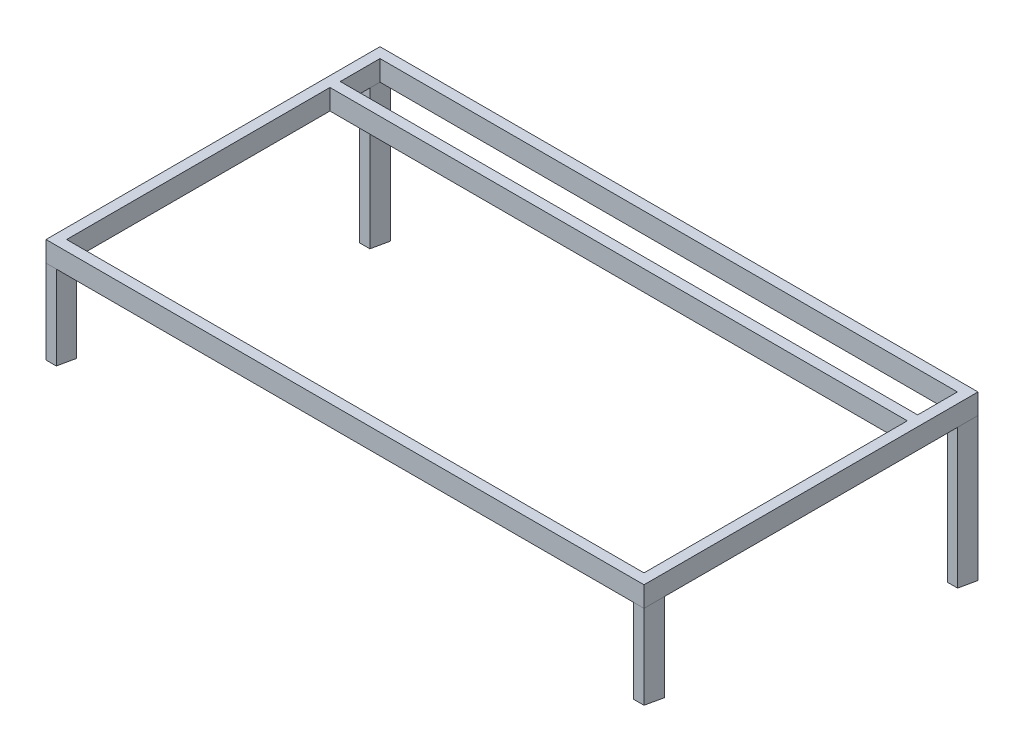
SolidWorks part; units mm, degrees
ref_plane "Front Plane" through (0, 0, 0) normal (0, 0, 1) x (1, 0, 0)
ref_plane "Top Plane" through (0, 0, 0) normal (0, 1, 0) x (1, 0, 0)
ref_plane "Right Plane" through (0, 0, 0) normal (1, 0, 0) x (0, 0, -1)
sketch "Sketch22" plane through (0, 0, 0) normal (0, 1, 0) x (1, 0, 0)
  line L0 (-712.1, 386.52) -> (712.1, 386.52)
  line L1 (-737.5, 411.92) -> (737.5, 411.92)
  line L2 (-737.5, 411.92) -> (-737.5, -411.92)
  line L3 (-737.5, -411.92) -> (737.5, -411.92)
  line L4 (737.5, 411.92) -> (737.5, -411.92)
  line L5 (-737.5, 411.92) -> (737.5, -411.92) construction
  line L6 (-737.5, -411.92) -> (737.5, 411.92) construction
  line L7 (712.1, 386.52) -> (712.1, -386.52)
  line L8 (-712.1, -386.52) -> (712.1, -386.52)
  line L9 (-712.1, 386.52) -> (-712.1, -386.52)
  point P0 (0, 0)
  dimension "D1" = 1475
  dimension "D2" = 823.84
  dimension "D3" = 25.4
extrude "Boss-Extrude3" add sketch "Sketch22" against normal blind 50.4
sketch "Sketch23" plane through (0, -50.4, 0) normal (0, -1, 0) x (1, 0, 0)
  line L0 (-712.1, -386.52) -> (-712.1, 386.52) construction
  line L1 (-737.5, 411.92) -> (-712.1, 411.92)
  line L2 (-737.5, 411.92) -> (-737.5, 361.52)
  line L3 (-737.5, 361.52) -> (-712.1, 361.52)
  line L4 (-712.1, 411.92) -> (-712.1, 361.52)
  line L5 (0, 0) -> (0, 277.5925) construction
  line L6 (712.1, 411.92) -> (712.1, 361.52)
  line L7 (737.5, 361.52) -> (712.1, 361.52)
  line L8 (737.5, 411.92) -> (737.5, 361.52)
  line L9 (737.5, 411.92) -> (712.1, 411.92)
  dimension "D1" = 50.4
extrude "Boss-Extrude4" add sketch "Sketch23" along normal blind 258.12 separate body
sketch "Sketch24" plane through (0, -50.4, 0) normal (0, -1, 0) x (1, 0, 0)
  line L0 (-712.1, -386.52) -> (-712.1, 386.52) construction
  line L1 (-737.5, -411.92) -> (-712.1, -411.92)
  line L2 (-737.5, -411.92) -> (-737.5, -361.52)
  line L3 (-737.5, -361.52) -> (-712.1, -361.52)
  line L4 (-712.1, -411.92) -> (-712.1, -361.52)
  line L5 (0, 0) -> (0, -131.3731) construction
  line L6 (712.1, -411.92) -> (712.1, -361.52)
  line L7 (737.5, -361.52) -> (712.1, -361.52)
  line L8 (737.5, -411.92) -> (737.5, -361.52)
  line L9 (737.5, -411.92) -> (712.1, -411.92)
  dimension "D1" = 50.4
extrude "Boss-Extrude5" add sketch "Sketch24" along normal blind 402.27 separate body
sketch "Sketch25" plane through (737.5, 0, 0) normal (1, 0, 0) x (0, 0, -1)
  line L0 (361.52, -393.9384) -> (411.92, -402.8253)
  line L2 (361.52, -452.67) -> (361.52, -50.4) construction
  line L3 (411.92, -452.67) -> (411.92, -50.4) construction
  line L4 (411.92, -402.8253) -> (411.92, -452.67)
  line L5 (411.92, -452.67) -> (-411.92, -452.67)
  line L6 (-411.92, -452.67) -> (-411.92, -257.5601)
  line L7 (-411.92, -308.52) -> (-411.92, -50.4) construction
  line L8 (-411.92, -257.5601) -> (-361.52, -266.447)
  line L9 (-361.52, -308.52) -> (-361.52, -50.4) construction
  line L10 (-361.52, -266.447) -> (-361.52, -308.52)
  line L11 (-361.52, -308.52) -> (361.52, -393.9384)
  line L12 (411.92, -50.4) -> (361.52, -50.4) construction
  dimension "D1" = 207.1601
  dimension "D2" = 216.047
extrude "Cut-Extrude1" cut sketch "Sketch25" against normal through all
sketch "Sketch26" plane through (0, 0, 0) normal (0, 1, 0) x (1, 0, 0)
  line L0 (-712.1, 386.52) -> (-712.1, -386.52) construction
  line L1 (-712.1, 288.45) -> (712.1, 288.45)
  line L2 (-712.1, 288.45) -> (-712.1, 263.05)
  line L3 (-712.1, 263.05) -> (712.1, 263.05)
  line L4 (712.1, 288.45) -> (712.1, 263.05)
  line L5 (712.1, -386.52) -> (712.1, 386.52) construction
  line L7 (712.1, 386.52) -> (-712.1, 386.52) construction
  dimension "D1" = 25.4
  dimension "D2" = 123.47
extrude "Boss-Extrude6" add sketch "Sketch26" against normal up to surface (50.4 mm away) up to face at (0, -50.4, 0)
